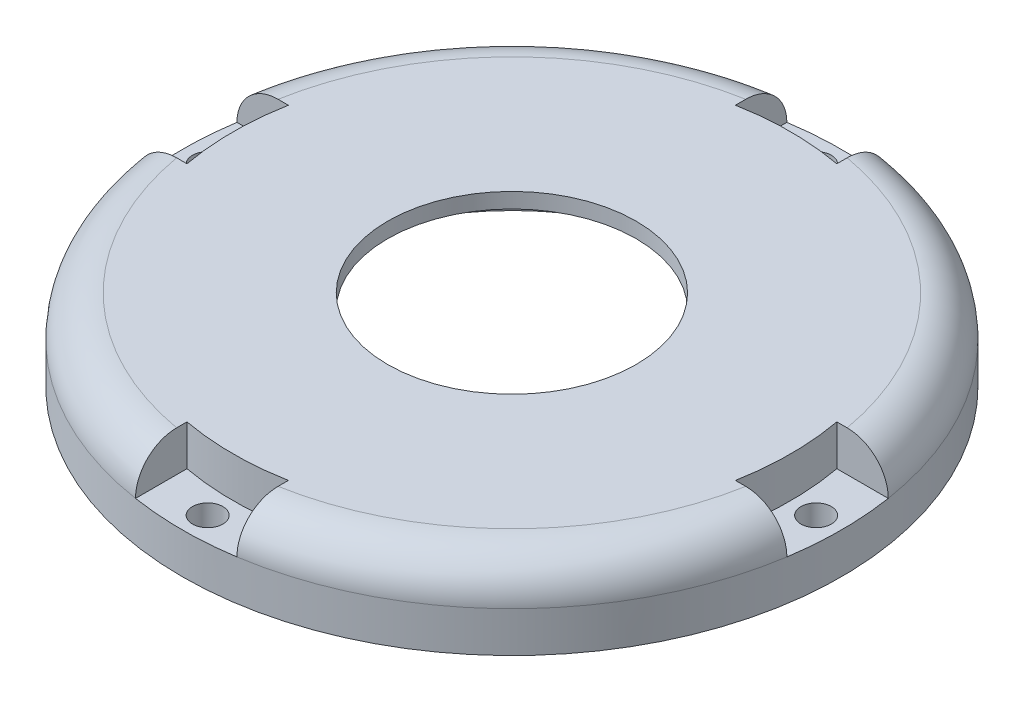
SolidWorks part; units mm, degrees
ref_plane "Front Plane" through (0, 0, 0) normal (0, 0, 1) x (1, 0, 0)
ref_plane "Top Plane" through (0, 0, 0) normal (0, 1, 0) x (1, 0, 0)
ref_plane "Right Plane" through (0, 0, 0) normal (1, 0, 0) x (0, 0, -1)
sketch "Sketch1" plane through (0, 0, 0) normal (0, 1, 0) x (1, 0, 0)
  circle A0 centre (0, 0) radius 32.5
  circle A1 centre (0, 0) radius 27.5
  dimension "D1" = 65
  dimension "D2" = 55
extrude "Boss-Extrude1" add sketch "Sketch1" along normal blind 4
sketch "Sketch2" plane through (0, 4, 0) normal (0, 1, 0) x (1, 0, 0)
  line L0 (0, 27.5) -> (0, 30) construction
  line L1 (-30, 0) -> (-30, 1.5) construction
  line L2 (-30, 0) -> (-30, -5) construction
  line L3 (-32.1131, -5) -> (-27.0416, -5)
  line L4 (-30, 5) -> (-32.1131, 5)
  line L5 (-32.1131, 5) -> (-27.0416, 5)
  line L6 (0, 30) -> (1.5, 30) construction
  line L7 (0, 30) -> (-1.5, 30) construction
  line L8 (-5, 32.1131) -> (-5, 27.0416)
  line L9 (5, 32.1131) -> (5, 27.0416)
  line L14 (-5, -27.0416) -> (-5, -32.1131)
  line L15 (5, -27.0416) -> (5, -32.1131)
  line L16 (27.0416, -5) -> (32.1131, -5)
  line L17 (27.0416, 5) -> (32.1131, 5)
  circle A0 centre (0, 0) radius 27.5 construction
  arc A5 (-32.1131, -5) -> (-5, -32.1131) centre (0, 0) ccw
  arc A6 (-27.0416, -5) -> (-5, -27.0416) centre (0, 0) ccw
  arc A7 (27.0416, 5) -> (5, 27.0416) centre (0, 0) ccw
  arc A8 (32.1131, 5) -> (5, 32.1131) centre (0, 0) ccw
  arc A9 (5, -27.0416) -> (27.0416, -5) centre (0, 0) ccw
  arc A10 (5, -32.1131) -> (32.1131, -5) centre (0, 0) ccw
  arc A11 (-5, 32.1131) -> (-32.1131, 5) centre (0, 0) ccw
  arc A12 (-5, 27.0416) -> (-27.0416, 5) centre (0, 0) ccw
  point P15 (0, 0)
  circle M12 centre (0, 0) radius 32.5
  circle M13 centre (0, 0) radius 27.5
  dimension "D4" = 5
  dimension "D1" = 2.5
  dimension "D5" = 5
extrude "Boss-Extrude2" add sketch "Sketch2" along normal blind 4 contours L8 L4 L5 M12 M13 | L14 L3 M13 M12 | L16 L15 M13 M12 | L17 L9 M13 M12 region at (-19.945, 4, 19.945) region at (-19.945, 4, -19.945) region at (19.945, 4, 19.945) region at (19.945, 4, -19.945)
sketch "Sketch3" plane through (0, 4, 0) normal (0, 1, 0) x (1, 0, 0)
  line L0 (0, 27.5) -> (0, 30) construction
  arc A0 (5, 27.0416) -> (-5, 27.0416) centre (0, 0) ccw construction
  circle A1 centre (0, 30) radius 1.5
  circle A2 centre (30, 0) radius 1.5
  circle A3 centre (0, -30) radius 1.5
  circle A4 centre (-30, 0) radius 1.5
  point P17 (0, 0)
  dimension "D2" = 3
  dimension "D1" = 2.5
  dimension "D3" = 4
extrude "Cut-Extrude1" cut sketch "Sketch3" against normal blind 6
sketch "Sketch7" plane through (0, 8, 0) normal (0, 1, 0) x (1, 0, 0)
  line L0 (-5, -32.1131) -> (-5, -27.0416) construction
  line L1 (-27.0416, -5) -> (-32.1131, -5) construction
  line L2 (32.1131, -5) -> (27.0416, -5) construction
  line L3 (5, -27.0416) -> (5, -32.1131) construction
  line L4 (27.0416, 5) -> (32.1131, 5) construction
  line L5 (5, 32.1131) -> (5, 27.0416) construction
  line L6 (-5, 27.0416) -> (-5, 32.1131) construction
  line L7 (-32.1131, 5) -> (-27.0416, 5) construction
  line L8 (-5, -32.1131) -> (-5, -27.0416)
  line L9 (-27.0416, -5) -> (-32.1131, -5)
  line L10 (32.1131, -5) -> (27.0416, -5)
  line L11 (5, -27.0416) -> (5, -32.1131)
  line L12 (27.0416, 5) -> (32.1131, 5)
  line L13 (5, 32.1131) -> (5, 27.0416)
  line L14 (-5, 27.0416) -> (-5, 32.1131)
  line L15 (-32.1131, 5) -> (-27.0416, 5)
  arc A0 (-27.0416, -5) -> (-5, -27.0416) centre (0, 0) ccw construction
  arc A1 (-32.1131, -5) -> (-5, -32.1131) centre (0, 0) ccw construction
  arc A2 (5, -27.0416) -> (27.0416, -5) centre (0, 0) ccw construction
  arc A3 (5, -32.1131) -> (32.1131, -5) centre (0, 0) ccw construction
  arc A4 (27.0416, 5) -> (5, 27.0416) centre (0, 0) ccw construction
  arc A5 (32.1131, 5) -> (5, 32.1131) centre (0, 0) ccw construction
  arc A6 (-5, 32.1131) -> (-32.1131, 5) centre (0, 0) ccw construction
  arc A7 (-5, 27.0416) -> (-27.0416, 5) centre (0, 0) ccw construction
  arc A8 (-27.0416, -5) -> (-5, -27.0416) centre (0, 0) ccw
  arc A9 (-32.1131, -5) -> (-5, -32.1131) centre (0, 0) ccw
  arc A10 (5, -27.0416) -> (27.0416, -5) centre (0, 0) ccw
  arc A11 (5, -32.1131) -> (32.1131, -5) centre (0, 0) ccw
  arc A12 (27.0416, 5) -> (5, 27.0416) centre (0, 0) ccw
  arc A13 (32.1131, 5) -> (5, 32.1131) centre (0, 0) ccw
  arc A14 (-5, 32.1131) -> (-32.1131, 5) centre (0, 0) ccw
  arc A15 (-5, 27.0416) -> (-27.0416, 5) centre (0, 0) ccw
  circle A16 centre (0, 0) radius 27.5
  circle A17 centre (0, 0) radius 15
  circle A18 centre (0, 0) radius 25
  line M10 (-5, 27.0416) -> (-5, 32.1131)
  arc M11 (-5, 32.1131) -> (-32.1131, 5) centre (0, 0) ccw
  line M12 (-32.1131, 5) -> (-27.0416, 5)
  arc M13 (-27.0416, 5) -> (-5, 27.0416) centre (0, 0) cw
  dimension "D1" = 30
  dimension "D2" = 50
extrude "Boss-Extrude4" add sketch "Sketch7" against normal blind 8 contours M13 M10 M11 M12 | L12 A13 L13 A12 | L11 A11 L10 A10 | L9 A9 L8 A8 | A10 A16 A12 A8 A18 M13 region at (-19.945, 8, 19.945) region at (-18.8954, 8, 18.8954) region at (19.945, 8, 19.945) region at (-19.945, 8, -19.945) region at (19.945, 8, -19.945)
sketch "Sketch8" plane through (0, 0, 0) normal (0, -1, 0) x (-1, 0, 0)
  circle A0 centre (0, 0) radius 27.5
  circle A1 centre (0, 0) radius 12.25
  dimension "D1" = 55
  dimension "D2" = 24.5
extrude "Boss-Extrude5" add sketch "Sketch8" against normal blind 4
sketch "Sketch10" plane through (0, 4, 0) normal (0, 1, 0) x (1, 0, 0)
  circle A0 centre (0, 0) radius 25
  circle A1 centre (0, 0) radius 12.25
  dimension "2" = 24.5
extrude "Boss-Extrude6" add sketch "Sketch10" along normal blind 4
fillet "Fillet3" radius 4 4 edges at (22.981, 8, -22.981) (22.981, 8, 22.981) (-22.981, 8, 22.981) (-22.981, 8, -22.981)
sketch "Sketch11" plane through (0, 0, 0) normal (0, -1, 0) x (1, 0, 0)
  circle A0 centre (0, 0) radius 21.25
  dimension "D1" = 42.5
extrude "Cut-Extrude2" cut sketch "Sketch11" against normal blind 4
sketch "Sketch14" plane through (0, 4, 0) normal (0, -1, 0) x (1, 0, 0)
  line L0 (0, 0) -> (0, 16) construction
  line L1 (0, 16) -> (0, 18.5) construction
  circle A0 centre (0, 0) radius 18.5
  dimension "D1" = 16
  dimension "D2" = 2.5
extrude "Cut-Extrude3" cut sketch "Sketch14" against normal blind 2.5
